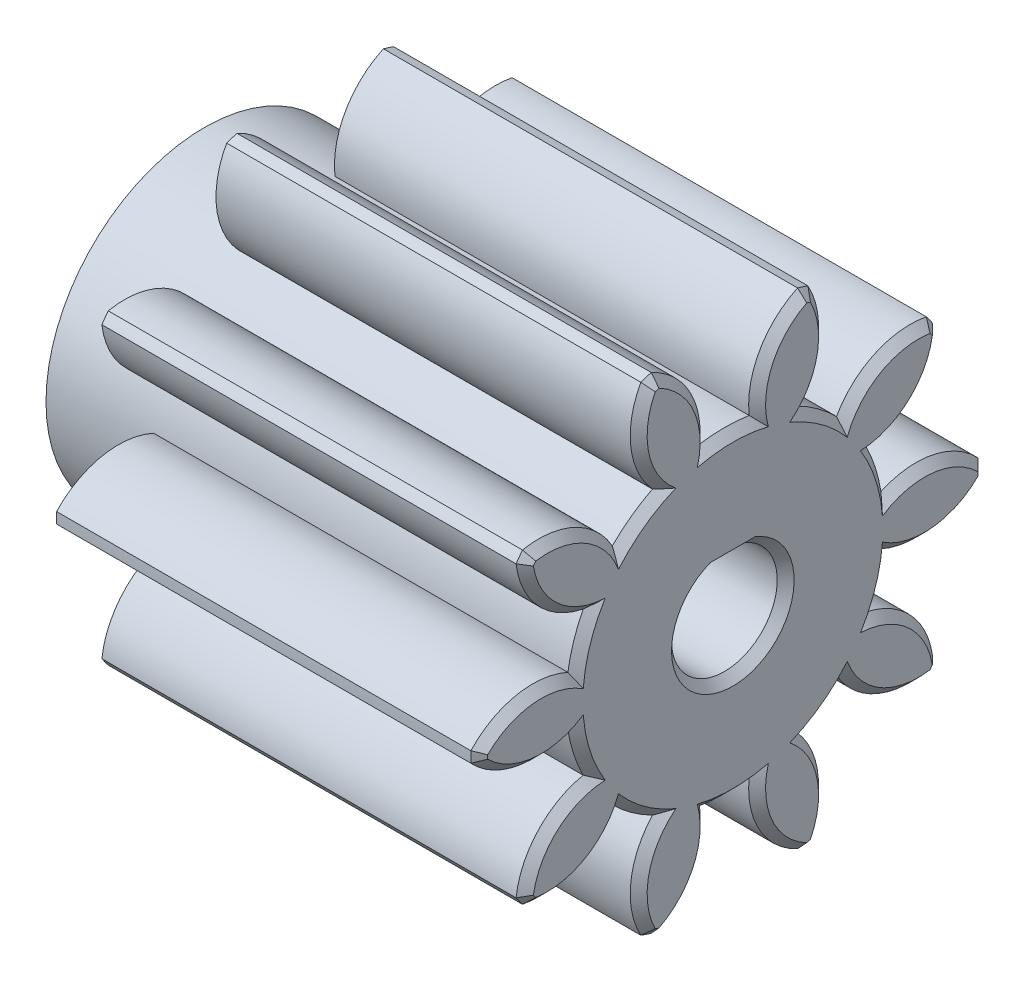
SolidWorks part; units mm, degrees
ref_plane "Plane1" through (0, 0, 0) normal (0, 0, 1) x (1, 0, 0)
ref_plane "Plane2" through (0, 0, 0) normal (0, 1, 0) x (1, 0, 0)
ref_plane "Plane3" through (0, 0, 0) normal (1, 0, 0) x (0, 0, -1)
other "Configuration Table"
sketch "HoldingSke" plane through (0, 0, 0) normal (0, 1, 0) x (1, 0, 0)
  line L0 (0, 0) -> (0.4924, -0.0868)
  line L1 (-15, 0) -> (100, 0) construction
  line L2 (0, 0) -> (-2.1039, 2.3779)
  line L3 (0, 0) -> (-11.863, 4.5341)
  line L4 (0, 0) -> (8.5048, 1.4996)
  line L5 (0, 0) -> (-28.1086, -10.4837)
  line L6 (0, 0) -> (-16.5793, -11.1861)
  line L7 (-2.1039, 2.3779) -> (4.3536, 31.6747)
  line L8 (-76.2, 54.61) -> (-75.3, 54.61)
  line L9 (-71.009, 38.7566) -> (-53.1078, 45.2721)
  line L10 (-76.2, 71.12) -> (104.1128, 71.12)
  line L11 (0, 0) -> (-20, 0)
  line L12 (-76.2, 101.6) -> (-76.133, 101.6)
  line L13 (24.9733, 27.94) -> (52.9518, 28.4284)
  line L14 (24.9733, 27.94) -> (24.9743, 27.94)
  line L15 (24.9733, 27.94) -> (100.4006, 29.5858)
  line L16 (-63.627, -2) -> (-12.827, -2)
  circle A0 centre (0, 0) radius 2.5
  circle A1 centre (0, 0) radius 7.499
  circle A2 centre (0, 0) radius 37.5
  circle A3 centre (0, 0) radius 2.5
  dimension "Num_teeth" = 10
  dimension "Pitch_radius" = 180.3128
  dimension "Width" = 20
  dimension "Thickness" = 20
sketch "BasProSke" plane through (0, 0, 0) normal (0, 1, 0) x (1, 0, 0)
  line L0 (-10, 0) -> (60, 0) construction
  line L1 (0, 0) -> (0, 12)
  line L2 (0, 0) -> (20, 0)
  line L3 (20, 0) -> (20, 12)
  line L4 (20, 12) -> (0, 12)
  dimension "Thickness" = 20
  dimension "Diameter" = 24
revolve "Base-Revolve" add sketch "BasProSke" angle 360 about L0
sketch "TooCutSke" plane through (0, 0, 0) normal (1, 0, 0) x (0, 0, -1)
  line L1 (0, 0) -> (0, 107) construction
  line L2 (0, 0) -> (-1.6814, 9.8576) construction
  line L3 (0, 0) -> (-6.1153, 18.8209) construction
  line L4 (-1.6814, 9.8576) -> (-3.0576, 9.4105) construction
  arc A0 (1.1737, 7.4066) -> (-1.1737, 7.4066) centre (0, 0) ccw
  arc A1 (3.4979, 11.5054) -> (-3.4979, 11.5054) centre (0, 0) ccw
  circle A2 centre (0, 0) radius 10 construction
  circle A3 centre (0, 0) radius 9.3969 construction
  arc A4 (-1.1737, 7.4066) -> (-3.4979, 11.5054) centre (-5.1477, 7.8615) ccw
  arc A5 (3.4979, 11.5054) -> (1.1737, 7.4066) centre (5.1477, 7.8615) ccw
extrude "ToothCut" cut sketch "TooCutSke" along normal through all
fillet "Breaks" [suppressed] radius 0.04 tangent propagation no
fillet "RootFillets" [suppressed] radius 0.501
pattern_circular "TeethCuts" count 10 every 36 about axis through (-10, 0, 0) along (1, 0, 0) of "ToothCut", "RootFillets", "Breaks"
sketch "HubNeaOneSke" plane through (0, 0, 0) normal (-1, 0, 0) x (0, 0, 1)
  circle A0 centre (0, 0) radius 7.499
  dimension "Diameter" = 14.998
extrude "HubNearOne" add sketch "HubNeaOneSke" along normal blind 10.0001
sketch "HubNeaBotSke" plane through (0, 0, 0) normal (-1, 0, 0) x (0, 0, 1)
  circle A0 centre (0, 0) radius 7.499
  dimension "Diameter" = 14.998
extrude "HubNearBoth" [suppressed] add sketch "HubNeaBotSke" along normal blind 5
ref_plane "FarPln" through (20, 0, 0) normal (1, 0, 0) x (0, 0, -1)
sketch "HubFarSke" plane through (20, 0, 0) normal (1, 0, 0) x (0, 0, -1)
  circle A0 centre (0, 0) radius 7.499
  dimension "Diameter" = 14.998
extrude "HubFar" [suppressed] add sketch "HubFarSke" along normal blind 5
sketch "BorSke" plane through (0, 0, 0) normal (1, 0, 0) x (0, 0, -1)
  circle A0 centre (0, 0) radius 2.5
  dimension "Diameter" = 5
extrude "Bore" cut sketch "BorSke" along normal mid plane 60.0001
sketch "KeySke" plane through (0, 0, 0) normal (1, 0, 0) x (0, 0, -1)
  line L0 (-1, 0) -> (-1, 3.4)
  line L1 (-1, 3.4) -> (1, 3.4)
  line L2 (1, 3.4) -> (1, 0)
  line L3 (0, 0) -> (0, 34) construction
  line L4 (-1, 0) -> (1, 0)
extrude "Keyway" [suppressed] cut sketch "KeySke" along normal mid plane 60.0001
pattern_circular "Keyway2" [suppressed] count 2 every 90 about axis through (-10, 0, 0) along (1, 0, 0) reverse direction yes
sketch "草图1" plane through (-10.0001, 0, 0) normal (-1, 0, 0) x (0, 0, 1)
  circle A0 centre (0, 0) radius 9.634
extrude "切除-拉伸1" cut sketch "草图1" against normal blind 5
sketch "草图2" plane through (20, 0, 0) normal (1, 0, 0) x (0, 0, -1)
  line L0 (-0.9798, 2.3) -> (0.9798, 2.3)
  arc A0 (0.9798, 2.3) -> (-0.9798, 2.3) centre (0, 0) ccw
  dimension "D2" = 5
  dimension "D1" = 2.3
extrude "凸台-拉伸1" add sketch "草图2" against normal up to surface (25.0001 mm away) up to face at (-5.0001, 0, 7.499)
chamfer "倒角1" distance 0.4 angle 45 42 edges at (20, 0, -12) (20, -1.4563, -9.8499) (20, -2.3173, -7.132) (20, -4.6115, -8.8248) (20, -7.0534, -9.7082) (20, -6.9678, -7.1128) (20, -6.0668, -4.4078) (20, -8.9178, -4.4288) (20, -11.4127, -3.7082) (20, -9.8179, -1.6588) (20, -7.499, 0) (20, -9.8179, 1.6588) (20, -11.4127, 3.7082) (20, -8.9178, 4.4288) (20, -6.0668, 4.4078) (20, -6.9678, 7.1128) (20, -7.0534, 9.7082) (20, -4.6115, 8.8248) (20, -2.3173, 7.132) (20, -1.4563, 9.8499) (20, 0, 12) (20, 1.4563, 9.8499) (20, 2.3173, 7.132) (20, 4.6115, 8.8248) (20, 7.0534, 9.7082) (20, 6.9678, 7.1128) (20, 6.0668, 4.4078) (20, 8.9178, 4.4288) (20, 11.4127, 3.7082) (20, 9.8179, 1.6588) (20, 7.499, 0) (20, 9.8179, -1.6588) (20, 11.4127, -3.7082) (20, 8.9178, -4.4288) (20, 6.0668, -4.4078) (20, 6.9678, -7.1128) (20, 7.0534, -9.7082) (20, 4.6115, -8.8248) (20, 2.3173, -7.132) (20, 1.4563, -9.8499) (20, 2.3, 0) (20, -2.5, 0)
equation "' \"Module@HoldingSke\" = 6.35"
equation "' \"Num_teeth@HoldingSke\" = 12"
equation "' \"Ap@HoldingSke\" =  20"
equation "' \"Ap@HoldingSke\" = 20"
equation "' \"Width@HoldingSke\" = 0.5 * 25.4"
equation "' \"Hub_dia@HoldingSke\"= 1 * 25.4"
equation "' \"Hub_dia@HoldingSke\" = 1 * 25.4"
equation "' \"Overall_len@HoldingSke\" = 1.0 * 25.4"
equation "' \"Bore@HoldingSke\" = 0.75 * 25.4"
equation "' \"T_dim@HoldingSke\" = 0.1 * 25.4"
equation "' \"Width@KeySke\" = 0.25 * 25.4"
equation "' \"Show_teeth@HoldingSke\" = 13"
equation "' \"Backlash@HoldingSke\" = 0.009 * 25.4"
equation "' \"Addendum_fac@HoldingSke\" = 1.0"
equation "' \"Dedendum_fac@HoldingSke\" = 1.25"
equation "' \"Dedendum_add@HoldingSke\" = 0.00005 * 25.4"
equation "' \"Clearance_fac@HoldingSke\" = 0.25"
equation "\"Pitch@HoldingSke\" = 1 / \"Module@HoldingSke\""
equation "\"Overcut_dia@TooCutSke\" = (\"Num_teeth@HoldingSke\" + 2 * \"Addendum_fac@HoldingSke\") / \"Pitch@HoldingSke\" + 0.002 * 25.4"
equation "\"Pitch_dia@TooCutSke\" = \"Num_teeth@HoldingSke\" / \"Pitch@HoldingSke\""
equation "\"Base_dia@TooCutSke\" = \"Num_teeth@HoldingSke\" / \"Pitch@HoldingSke\" * cos((\"Ap@HoldingSke\"  * 3.14159265 / 180))"
equation "\"Root_dia@TooCutSke\" = (\"Num_teeth@HoldingSke\" + 2) / \"Pitch@HoldingSke\" - 2 * (\"Addendum_fac@HoldingSke\" + \"Dedendum_fac@HoldingSke\") / \"Pitch@HoldingSke\" - \"Dedendum_add@HoldingSke\" * 2"
equation "\"Half_ang@TooCutSke\" = 180 / \"Num_teeth@HoldingSke\""
equation "\"Half_CT@TooCutSke\" = \"Num_teeth@HoldingSke\" / \"Pitch@HoldingSke\" * sin((3.14159265 / 2 / \"Num_teeth@HoldingSke\")) / 2 - 7 * \"Backlash@HoldingSke\" / 4"
equation "\"Flank_rad@TooCutSke\" = \"Num_teeth@HoldingSke\" / \"Pitch@HoldingSke\" / 5"
equation "\"Radius@RootFillets\" = \"Clearance_fac@HoldingSke\" / \"Pitch@HoldingSke\" + \"Dedendum_add@HoldingSke\""
equation "\"Break_rad@Breaks\" = 0.02 / \"Pitch@HoldingSke\""
equation "\"Thickness@HoldingSke\" = \"Width@HoldingSke\""
equation "\"OAL@HoldingSke\" = \"Thickness@HoldingSke\""
equation "\"MHD@HoldingSke\" = (\"Num_teeth@HoldingSke\" + 2) / \"Pitch@HoldingSke\" - 2 * (\"Addendum_fac@HoldingSke\" + \"Dedendum_fac@HoldingSke\")  / \"Pitch@HoldingSke\" - \"Dedendum_add@HoldingSke\" * 2"
equation "\"MBD@HoldingSke\" = (\"Num_teeth@HoldingSke\" + 2) / \"Pitch@HoldingSke\" - 2 * (\"Addendum_fac@HoldingSke\" + \"Dedendum_fac@HoldingSke\")  / \"Pitch@HoldingSke\" - \"Dedendum_add@HoldingSke\" * 2 - 0.002 * 25.4"
equation "\"MHD@HoldingSke\" = ((sgn( \"MHD@HoldingSke\" - \"Hub_dia@HoldingSke\" )-1)*( \"MHD@HoldingSke\" - \"Hub_dia@HoldingSke\" ))/-2+ \"Hub_dia@HoldingSke\""
equation "\"MBD@HoldingSke\" = ((sgn( \"MBD@HoldingSke\" - \"Bore@HoldingSke\" )-1)*( \"MBD@HoldingSke\" - \"Bore@HoldingSke\" ))/-2+ \"Bore@HoldingSke\""
equation "\"OAL@HoldingSke\" = ((sgn( \"OAL@HoldingSke\" - \"Overall_len@HoldingSke\" )+1)*( \"OAL@HoldingSke\" - \"Overall_len@HoldingSke\" ))/2 + \"Overall_len@HoldingSke\" + 0.000002 * 25.4"
equation "\"Num_teeth@TeethCuts\" = int( \"Show_teeth@HoldingSke\" ) + 1"
equation "\"Num_teeth@TeethCuts\" = ((sgn( \"Num_teeth@TeethCuts\" - \"Num_teeth@HoldingSke\" )-1)*( \"Num_teeth@TeethCuts\" - \"Num_teeth@HoldingSke\" ))/-2+ \"Num_teeth@HoldingSke\""
equation "\"Num_teeth@TeethCuts\" = ((sgn( \"Num_teeth@TeethCuts\" - 2.0)+1)*( \"Num_teeth@TeethCuts\" - 2.0))/2 +2.0"
equation "\"Angle@TeethCuts\" = 360.0 / \"Num_teeth@HoldingSke\""
equation "\"Diameter@BasProSke\" = (\"Num_teeth@HoldingSke\" + 2 * \"Addendum_fac@HoldingSke\") / \"Pitch@HoldingSke\""
equation "\"Thickness@BasProSke\"  = \"Thickness@HoldingSke\""
equation "' \"Fillet_rad@BasProSke\" =  \"Thickness@HoldingSke\" * 0.05"
equation "' \"Fillet_rad@BasProSke\" = \"Thickness@HoldingSke\" * 0.05"
equation "\"MHD@HoldingSke\" = ((sgn( \"MHD@HoldingSke\" - \"Root_dia@TooCutSke\" )-1)*( \"MHD@HoldingSke\" - \"Root_dia@TooCutSke\" ))/-2+ \"Root_dia@TooCutSke\""
equation "\"Diameter@HubNeaOneSke\" = \"MHD@HoldingSke\""
equation "\"Length@HubNearOne\" = \"OAL@HoldingSke\" - \"Thickness@BasProSke\""
equation "\"Diameter@HubNeaBotSke\" = \"MHD@HoldingSke\""
equation "\"Length@HubNearBoth\" = ( \"OAL@HoldingSke\" - \"Thickness@BasProSke\" ) / 2.0"
equation "\"Thickness@FarPln\" = \"Thickness@BasProSke\""
equation "\"Diameter@HubFarSke\" = \"MHD@HoldingSke\""
equation "\"Length@HubFar\" = ( \"OAL@HoldingSke\" - \"Thickness@BasProSke\" ) / 2.0"
equation "\"Diameter@BorSke\" = \"MBD@HoldingSke\""
equation "\"D1@Bore\" = \"OAL@HoldingSke\" * 2.0"
equation "\"D1@Keyway\" = \"OAL@HoldingSke\" * 2.0"
equation "\"Offset@KeySke\" = \"T_dim@HoldingSke\" + \"MBD@HoldingSke\" / 2.0"
